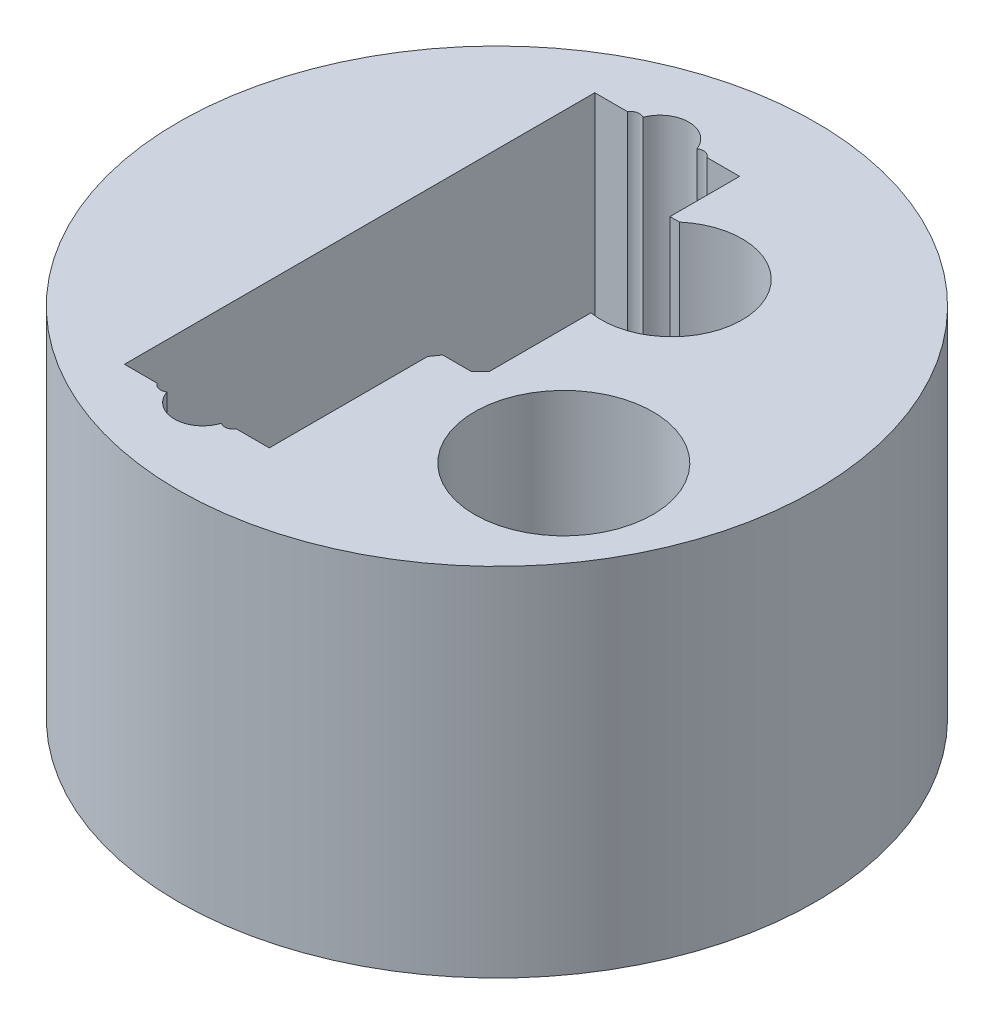
SolidWorks part; units mm, degrees
material "Polyurethane Foam Flexible"
ref_plane "Front Plane" through (0, 0, 0) normal (0, 0, 1) x (1, 0, 0)
ref_plane "Top Plane" through (0, 0, 0) normal (0, 1, 0) x (1, 0, 0)
ref_plane "Right Plane" through (0, 0, 0) normal (1, 0, 0) x (0, 0, -1)
sketch "Sketch1" plane through (0, 0, 0) normal (0, 1, 0) x (1, 0, 0)
  circle A0 centre (0, 0) radius 90.805
  dimension "D1" = 181.61
extrude "Boss-Extrude1" add sketch "Sketch1" along normal blind 101.6
sketch "Sketch2" plane through (0, 101.6, 0) normal (0, 1, 0) x (1, 0, 0)
  line L0 (38.735, 10.9339) -> (16.9053, 10.9339)
  line L1 (38.735, 74.295) -> (-38.735, 74.295)
  line L2 (38.735, 74.295) -> (38.735, 10.9339)
  line L3 (16.9053, -74.295) -> (-38.735, -74.295)
  line L4 (-38.735, 74.295) -> (-38.735, -74.295)
  line L5 (38.735, 74.295) -> (-38.735, -74.295) construction
  line L6 (38.735, -74.295) -> (-38.735, 74.295) construction
  line L7 (16.9053, 10.9339) -> (16.9053, -74.295)
  line L8 (16.9053, -74.295) -> (38.735, -74.295) construction
  line L9 (38.735, -74.295) -> (38.735, 10.9339) construction
  point P0 (0, 0)
  dimension "D1" = 77.47
  dimension "D2" = 148.59
extrude "Cut-Extrude1" [suppressed] cut sketch "Sketch2" against normal blind 203.2
sketch "Sketch3" plane through (0, 101.6, 0) normal (0, 1, 0) x (1, 0, 0)
  line L0 (0, 0) -> (-44.45, 0) construction
  line L1 (-74.45, 42.5) -> (-44.45, 42.5)
  line L2 (-74.45, 42.5) -> (-74.45, -42.5)
  line L3 (-74.45, -42.5) -> (-44.45, -42.5)
  line L4 (-44.45, 42.5) -> (-44.45, -42.5)
  line L5 (0, 0) -> (0, 90.805) construction
  circle A0 centre (0, 0) radius 90.805 construction
  point P6 (-44.45, 0)
  dimension "D1" = 30
  dimension "D2" = 85
  dimension "D3" = 44.45
extrude "Cut-Extrude2" [suppressed] cut sketch "Sketch3" against normal blind 130
ref_plane "Plane1" [suppressed] through (0, 0, 0) normal (-1, 0, 0) x (0, 0, 1)
sketch "Sketch4" [suppressed] plane through (0, 101.6, 0) normal (0, 1, 0) x (1, 0, 0)
  line L0 (38.735, 10.9339) -> (38.735, 74.295) construction
  circle A0 centre (64.135, 0) radius 15.24
  dimension "D1" = 30.48
  dimension "D2" = 25.4
extrude "Cut-Extrude3" [suppressed] cut sketch "Sketch4" against normal up to surface (203.2 mm away) up to face at (0, 0, 90.805)
sketch "Sketch5" plane through (0, 0, 0) normal (0, -1, 0) x (-1, 0, 0)
  circle A0 centre (53.34, -3.3939) radius 15.24
  dimension "D1" = 30.48
  dimension "D2" = 53.34
extrude "Cut-Extrude4" [suppressed] cut sketch "Sketch5" against normal blind 63.5
sketch "Sketch6" plane through (0, 101.6, 0) normal (0, 1, 0) x (1, 0, 0)
  line L12 (12.5368, -19.7703) -> (4.318, -19.7703)
  line L13 (4.318, -19.7703) -> (2.54, -22.2945)
  line L14 (2.54, -22.2945) -> (2.54, -67.4084)
  line L15 (2.54, -67.4084) -> (-6.7508, -67.4084)
  line L16 (-29.4442, -67.4084) -> (-38.735, -67.4084)
  line L17 (-38.735, -67.4084) -> (-38.735, 66.6179)
  line L18 (-38.735, 66.6179) -> (-29.4442, 66.6179)
  line L19 (-6.7508, 66.6179) -> (2.54, 66.6179)
  line L20 (2.54, 46.7412) -> (5.2832, 46.796)
  line L21 (2.54, 66.6179) -> (2.54, 46.7412)
  line L22 (15.0368, 11.7523) -> (15.0368, -17.2703)
  line L23 (15.0368, -17.2703) -> (12.5368, -19.7703)
  arc A7 (-10.374, -68.17) -> (-6.7508, -67.4084) centre (-8.9432, -65.9776) ccw
  arc A8 (-25.821, -68.17) -> (-10.374, -68.17) centre (-18.0975, -65.711) ccw
  arc A9 (-29.4442, -67.4084) -> (-25.821, -68.17) centre (-27.2518, -65.9776) ccw
  arc A10 (-6.7508, 66.6179) -> (-10.374, 67.3795) centre (-8.9432, 65.1871) ccw
  arc A11 (-10.374, 67.3795) -> (-25.8068, 67.4211) centre (-18.0981, 64.5489) ccw
  arc A12 (-25.8068, 67.4211) -> (-29.4442, 66.6179) centre (-27.2239, 65.2008) ccw
  arc A13 (15.0368, 11.7523) -> (5.2832, 46.796) centre (18.2817, 31.5346) ccw
  point P0 (12.5368, -19.7703)
extrude "Cut-Extrude5" cut sketch "Sketch6" against normal up to surface (101.6 mm away) up to face at (0, 0, 90.805)
sketch "Sketch7" plane through (0, 101.6, 0) normal (0, 1, 0) x (1, 0, 0)
  circle A0 centre (48.26, -29.21) radius 25.4
  dimension "D3" = 50.8
  dimension "D1" = 48.26
  dimension "D2" = 29.21
extrude "Cut-Extrude6" cut sketch "Sketch7" against normal up to surface (101.6 mm away) up to face at (-6.9697, 0, -1.5184)
ref_plane "Plane2" through (22.86, 0, 0) normal (1, 0, 0) x (0, 0, -1)
